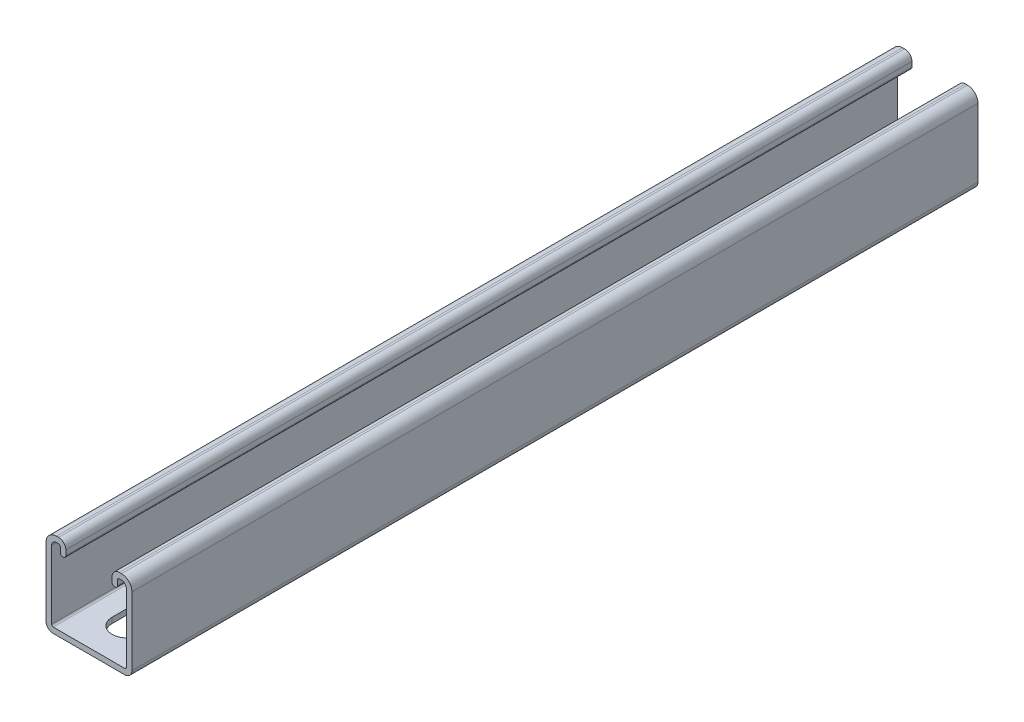
SolidWorks part; units mm, degrees
other "DetailItem6"
ref_plane "Front Plane" through (0, 0, 0) normal (0, 0, 1) x (1, 0, 0)
ref_plane "Top Plane" through (0, 0, 0) normal (0, 1, 0) x (1, 0, 0)
ref_plane "Right Plane" through (0, 0, 0) normal (1, 0, 0) x (0, 0, -1)
ref_plane "Plane1" through (0, 0, 3048) normal (0, 0, 1) x (1, 0, 0)
sketch "Sketch1" plane through (0, 0, 0) normal (0, 0, 1) x (1, 0, 0)
  line L0 (-20.6377, 0) -> (-17.9706, 0) construction
  line L1 (20.6377, 0) -> (17.9706, 0) construction
  line L2 (17.1769, -17.9704) -> (-17.1769, -17.9704)
  line L3 (-17.9706, -17.1766) -> (-17.9706, 15.5891)
  line L4 (-15.5894, 17.9704) -> (-14.5734, 17.9704)
  line L5 (-13.7797, 17.1766) -> (-13.7797, 14.8335)
  line L6 (-11.1127, 14.8335) -> (-11.1127, 17.1766)
  line L7 (-14.5734, 20.6374) -> (-15.5894, 20.6374)
  line L8 (-20.6377, 15.5891) -> (-20.6377, -17.1766)
  line L9 (-17.1769, -20.6374) -> (17.1769, -20.6374)
  line L10 (20.6377, 15.5891) -> (20.6377, -17.1766)
  line L11 (14.5734, 20.6374) -> (15.5894, 20.6374)
  line L12 (11.1127, 14.8335) -> (11.1127, 17.1766)
  line L13 (13.7797, 17.1766) -> (13.7797, 14.8335)
  line L14 (0, -17.9704) -> (0, -20.6374) construction
  line L15 (15.5894, 17.9704) -> (14.5734, 17.9704)
  line L16 (17.9706, -17.1766) -> (17.9706, 15.5891)
  arc A0 (-17.1769, -20.6374) -> (-20.6377, -17.1766) centre (-17.1769, -17.1766) cw
  arc A1 (-17.1769, -17.9704) -> (-17.9706, -17.1766) centre (-17.1769, -17.1766) cw
  arc A2 (-17.9706, 15.5891) -> (-15.5894, 17.9704) centre (-15.5894, 15.5891) cw
  arc A3 (-20.6377, 15.5891) -> (-15.5894, 20.6374) centre (-15.5894, 15.5891) cw
  arc A4 (-14.5734, 17.9704) -> (-13.7797, 17.1766) centre (-14.5734, 17.1766) cw
  arc A5 (-14.5734, 20.6374) -> (-11.1127, 17.1766) centre (-14.5734, 17.1766) cw
  arc A6 (-13.7797, 14.8335) -> (-11.1127, 14.8335) centre (-12.4462, 14.8335) ccw
  arc A7 (13.7797, 14.8335) -> (11.1127, 14.8335) centre (12.4462, 14.8335) cw
  arc A8 (14.5734, 20.6374) -> (11.1127, 17.1766) centre (14.5734, 17.1766) ccw
  arc A9 (14.5734, 17.9704) -> (13.7797, 17.1766) centre (14.5734, 17.1766) ccw
  arc A10 (20.6377, 15.5891) -> (15.5894, 20.6374) centre (15.5894, 15.5891) ccw
  arc A11 (17.9706, 15.5891) -> (15.5894, 17.9704) centre (15.5894, 15.5891) ccw
  arc A12 (17.1769, -17.9704) -> (17.9706, -17.1766) centre (17.1769, -17.1766) ccw
  arc A13 (17.1769, -20.6374) -> (20.6377, -17.1766) centre (17.1769, -17.1766) ccw
  dimension "D4" = 3.4608
  dimension "D5" = 5.0483
  dimension "D7" = 3.4608
  dimension "D1" = 34.3538
  dimension "D2" = 41.2748
  dimension "D3" = 2.667
  dimension "D6" = 1.016
  dimension "D8" = 2.3432
extrude "Primary Extrusion" add sketch "Sketch1" against normal blind 406.4
sketch "Sketch58" plane through (0, -20.6374, 0) normal (0, 1, 0) x (-1, 0, 0)
  line L0 (7.1438, -32.5438) -> (7.1438, -18.2562)
  line L1 (-7.1438, -18.2563) -> (-7.1438, -32.5438)
  line L2 (0, 22.7012) -> (0, -22.7012) construction
  line L3 (-7.1438, -25.4) -> (7.1438, -25.4) construction
  line L4 (17.1769, 0) -> (-17.1769, 0) construction
  arc A0 (7.1438, -32.5438) -> (-7.1438, -32.5438) centre (0, -32.5438) cw
  arc A1 (-7.1438, -18.2563) -> (7.1438, -18.2562) centre (0, -18.2563) cw
  dimension "D1" = 14.2875
  dimension "D2" = 14.2875
  dimension "D3" = 25.4
extrude "Slot Cut" cut sketch "Sketch58" along normal up to next contours L0 A1 L1 A0
pattern_linear "LPattern1" count 8 spacing 50.8 along (0, 0, -1) of "Slot Cut"
